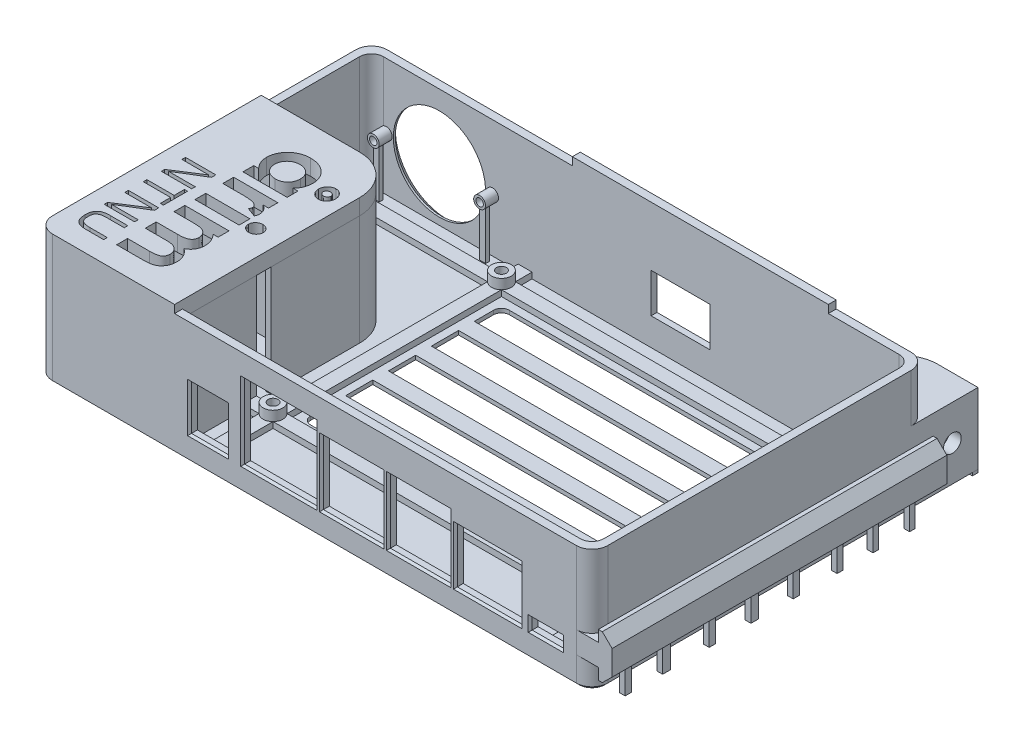
SolidWorks part; units mm, degrees
ref_plane "Plan de face" through (0, 0, 0) normal (0, 0, 1) x (1, 0, 0)
ref_plane "Plan de dessus" through (0, 0, 0) normal (0, 1, 0) x (1, 0, 0)
ref_plane "Plan de droite" through (0, 0, 0) normal (1, 0, 0) x (0, 0, -1)
sketch "Esquisse1" plane through (0, 0, 0) normal (0, 1, 0) x (1, 0, 0)
  line L2 (-70.5, -42.5) -> (70.5, -42.5)
  line L3 (-70.5, -42.5) -> (-70.5, 42.5)
  line L4 (-70.5, 42.5) -> (70.5, 42.5)
  line L5 (70.5, -42.5) -> (70.5, 42.5)
  line L6 (-70.5, -42.5) -> (70.5, 42.5) construction
  line L7 (-70.5, 42.5) -> (70.5, -42.5) construction
  point P2 (0, 0)
  dimension "D1" = 141
  dimension "D2" = 85
extrude "Main body" add sketch "Esquisse1" along normal blind 31
sketch "Esquisse2" plane through (0, 31, 0) normal (0, 1, 0) x (1, 0, 0)
  line L0 (70.5, -42.5) -> (70.5, 42.5) construction
  line L1 (-68.5, -40.5) -> (68.5, -40.5)
  line L2 (-68.5, -40.5) -> (-68.5, 40.5)
  line L3 (-68.5, 40.5) -> (68.5, 40.5)
  line L4 (68.5, -40.5) -> (68.5, 40.5)
  line L5 (-68.5, -40.5) -> (68.5, 40.5) construction
  line L6 (-68.5, 40.5) -> (68.5, -40.5) construction
  line L7 (70.5, 42.5) -> (-70.5, 42.5) construction
  point P0 (0, 0)
  dimension "D1" = 2
  dimension "D2" = 2
extrude "Body slot" cut sketch "Esquisse2" against normal blind 30
sketch "Esquisse3" plane through (0, 0, 42.5) normal (0, 0, 1) x (1, 0, 0)
  line L0 (68.5, 1) -> (68.5, 31) construction
  line L1 (55, 6.5) -> (62.5, 6.5) construction
  line L2 (55, 6.5) -> (55, 9) construction
  line L3 (55, 9) -> (62.5, 9) construction
  line L4 (62.5, 6.5) -> (62.5, 9) construction
  line L5 (55, 6.5) -> (62.5, 9) construction
  line L6 (55, 9) -> (62.5, 6.5) construction
  line L7 (68.5, 1) -> (-68.5, 1) construction
  line L9 (62.7, 6.3) -> (54.8, 6.3)
  line L10 (62.7, 6.3) -> (62.7, 9.2)
  line L11 (62.7, 9.2) -> (54.8, 9.2)
  line L12 (54.8, 6.3) -> (54.8, 9.2)
  line L13 (62.7, 6.3) -> (54.8, 9.2) construction
  line L14 (62.7, 9.2) -> (54.8, 6.3) construction
  line L15 (52, 6.5) -> (36, 6.5) construction
  line L16 (52, 6.5) -> (52, 20) construction
  line L17 (52, 20) -> (36, 20) construction
  line L18 (36, 6.5) -> (36, 20) construction
  line L19 (52, 6.5) -> (36, 20) construction
  line L20 (52, 20) -> (36, 6.5) construction
  line L21 (34, 6.5) -> (19, 6.5) construction
  line L22 (34, 6.5) -> (34, 22.5) construction
  line L23 (34, 22.5) -> (19, 22.5) construction
  line L24 (19, 6.5) -> (19, 22.5) construction
  line L25 (34, 6.5) -> (19, 22.5) construction
  line L26 (34, 22.5) -> (19, 6.5) construction
  line L27 (17, 6.5) -> (2, 6.5) construction
  line L28 (17, 6.5) -> (17, 22.5) construction
  line L29 (17, 22.5) -> (2, 22.5) construction
  line L30 (2, 6.5) -> (2, 22.5) construction
  line L31 (17, 6.5) -> (2, 22.5) construction
  line L32 (17, 22.5) -> (2, 6.5) construction
  line L33 (0, 6.5) -> (-18, 6.5) construction
  line L34 (0, 6.5) -> (0, 25) construction
  line L35 (0, 25) -> (-18, 25) construction
  line L36 (-18, 6.5) -> (-18, 25) construction
  line L37 (0, 6.5) -> (-18, 25) construction
  line L38 (0, 25) -> (-18, 6.5) construction
  line L39 (-22.5, 6.5) -> (-31.5, 6.5) construction
  line L40 (-22.5, 6.5) -> (-22.5, 17.5) construction
  line L41 (-22.5, 17.5) -> (-31.5, 17.5) construction
  line L42 (-31.5, 6.5) -> (-31.5, 17.5) construction
  line L43 (-22.5, 6.5) -> (-31.5, 17.5) construction
  line L44 (-22.5, 17.5) -> (-31.5, 6.5) construction
  line L45 (35.8, 6.3) -> (52.2, 6.3)
  line L46 (35.8, 6.3) -> (35.8, 20.2)
  line L47 (35.8, 20.2) -> (52.2, 20.2)
  line L48 (52.2, 6.3) -> (52.2, 20.2)
  line L49 (35.8, 6.3) -> (52.2, 20.2) construction
  line L50 (35.8, 20.2) -> (52.2, 6.3) construction
  line L51 (34.2, 6.3) -> (18.8, 6.3)
  line L52 (34.2, 6.3) -> (34.2, 22.7)
  line L53 (34.2, 22.7) -> (18.8, 22.7)
  line L54 (18.8, 6.3) -> (18.8, 22.7)
  line L55 (34.2, 6.3) -> (18.8, 22.7) construction
  line L56 (34.2, 22.7) -> (18.8, 6.3) construction
  line L57 (17.2, 6.3) -> (1.8, 6.3)
  line L58 (17.2, 6.3) -> (17.2, 22.7)
  line L59 (17.2, 22.7) -> (1.8, 22.7)
  line L60 (1.8, 6.3) -> (1.8, 22.7)
  line L61 (17.2, 6.3) -> (1.8, 22.7) construction
  line L62 (17.2, 22.7) -> (1.8, 6.3) construction
  line L63 (0.2, 6.3) -> (-18.2, 6.3)
  line L64 (0.2, 6.3) -> (0.2, 25.2)
  line L65 (0.2, 25.2) -> (-18.2, 25.2)
  line L66 (-18.2, 6.3) -> (-18.2, 25.2)
  line L67 (0.2, 6.3) -> (-18.2, 25.2) construction
  line L68 (0.2, 25.2) -> (-18.2, 6.3) construction
  line L69 (-22.3, 6.3) -> (-31.7, 6.3)
  line L70 (-22.3, 6.3) -> (-22.3, 17.7)
  line L71 (-22.3, 17.7) -> (-31.7, 17.7)
  line L72 (-31.7, 6.3) -> (-31.7, 17.7)
  line L73 (-22.3, 6.3) -> (-31.7, 17.7) construction
  line L74 (-22.3, 17.7) -> (-31.7, 6.3) construction
  point P0 (58.75, 7.75)
  point P5 (44, 13.25)
  point P10 (58.75, 7.75)
  point P19 (26.5, 14.5)
  point P24 (9.5, 14.5)
  point P29 (-9, 15.75)
  point P34 (-27, 12)
  point P39 (44, 13.25)
  point P44 (26.5, 14.5)
  point P49 (9.5, 14.5)
  point P54 (-9, 15.75)
  point P59 (-27, 12)
  dimension "D1" = 2.5
  dimension "D2" = 7.5
  dimension "D3" = 6
  dimension "D4" = 5.5
  dimension "D5" = 0.2
  dimension "D6" = 0.2
  dimension "D7" = 16
  dimension "D8" = 13.5
  dimension "D9" = 5.5
  dimension "D10" = 26.5
  dimension "D11" = 15
  dimension "D12" = 16
  dimension "D13" = 5.5
  dimension "D14" = 33
  dimension "D15" = 5.5
  dimension "D16" = 32
  dimension "D17" = 18
  dimension "D18" = 18.5
  dimension "D19" = 5.5
  dimension "D20" = 35
  dimension "D21" = 9
  dimension "D22" = 11
  dimension "D23" = 5.5
  dimension "D24" = 48.5
  dimension "D25" = 0.2
  dimension "D26" = 0.2
  dimension "D27" = 0.2
  dimension "D28" = 0.2
  dimension "D29" = 0.2
  dimension "D30" = 0.2
  dimension "D31" = 0.2
  dimension "D32" = 0.2
  dimension "D33" = 0.2
  dimension "D34" = 0.2
extrude "Jetson ports slot" cut sketch "Esquisse3" against normal blind 2
sketch "Esquisse4" plane through (0, 0, -42.5) normal (0, 0, -1) x (-1, 0, 0)
  line L0 (-68.5, 1) -> (-68.5, 31) construction
  line L1 (-4.5, 12) -> (-15.5, 12) construction
  line L2 (-4.5, 12) -> (-4.5, 14) construction
  line L3 (-4.5, 14) -> (-15.5, 14) construction
  line L4 (-15.5, 12) -> (-15.5, 14) construction
  line L5 (-4.5, 12) -> (-15.5, 14) construction
  line L6 (-4.5, 14) -> (-15.5, 12) construction
  line L7 (-68.5, 1) -> (68.5, 1) construction
  line L8 (68.5, 1) -> (68.5, 31) construction
  line L9 (-2.5, 8) -> (-17.5, 8)
  line L10 (-2.5, 8) -> (-2.5, 18)
  line L11 (-2.5, 18) -> (-17.5, 18)
  line L12 (-17.5, 8) -> (-17.5, 18)
  line L13 (-2.5, 8) -> (-17.5, 18) construction
  line L14 (-2.5, 18) -> (-17.5, 8) construction
  line L15 (67.5, 2.5) -> (35, 2.5) construction
  line L16 (67.5, 2.5) -> (67.5, 26.5) construction
  line L17 (67.5, 26.5) -> (35, 26.5) construction
  line L18 (35, 2.5) -> (35, 26.5) construction
  line L19 (67.5, 2.5) -> (35, 26.5) construction
  line L20 (67.5, 26.5) -> (35, 2.5) construction
  circle A0 centre (51.25, 14.5) radius 11.7
  point P0 (-10, 13)
  point P9 (-10, 13)
  point P14 (51.25, 14.5)
  dimension "D11" = 23.4
  dimension "D1" = 64
  dimension "D2" = 13
  dimension "D3" = 11
  dimension "D4" = 2
  dimension "D5" = 4
  dimension "D6" = 2
  dimension "D7" = 1
  dimension "D8" = 1.5
  dimension "D9" = 24
  dimension "D10" = 32.5
extrude "Sensor & SD slot" cut sketch "Esquisse4" against normal blind 2
fillet "Body corners" radius 4 4 edges at (70.5, 15.5, 42.5) (-70.5, 15.5, 42.5) (-70.5, 15.5, -42.5) (70.5, 15.5, -42.5)
fillet "Body interior corners" radius 3 4 edges at (68.5, 16, 40.5) (-68.5, 16, 40.5) (-68.5, 16, -40.5) (68.5, 16, -40.5)
chamfer "Body chanf" distance 0.75 angle 45 8 edges at (0, 0, 42.5) (69.3284, 0, 41.3284) (-69.3284, 0, 41.3284) (70.5, 0, 0) (-70.5, 0, 0) (69.3284, 0, -41.3284) (-69.3284, 0, -41.3284) (0, 0, -42.5)
chamfer "Ports chanf" distance 0.5 angle 45 28 edges at (17.5, 13, -42.5) (54.8, 7.75, 42.5) (58.75, 9.2, 42.5) (62.7, 7.75, 42.5) (58.75, 6.3, 42.5) (44, 20.2, 42.5) (52.2, 13.25, 42.5) (44, 6.3, 42.5) (35.8, 13.25, 42.5) (34.2, 14.5, 42.5) (26.5, 22.7, 42.5) (26.5, 6.3, 42.5) (18.8, 14.5, 42.5) (17.2, 14.5, 42.5) (9.5, 22.7, 42.5) (9.5, 6.3, 42.5) (1.8, 14.5, 42.5) (0.2, 15.75, 42.5) (-9, 25.2, 42.5) (-9, 6.3, 42.5) (-18.2, 15.75, 42.5) (-27, 17.7, 42.5) (-22.3, 12, 42.5) (-27, 6.3, 42.5) (-31.7, 12, 42.5) (2.5, 13, -42.5) (10, 8, -42.5) (10, 18, -42.5)
chamfer "Motion sensor chanf" distance 1.5 angle 45 1 edges at (-62.95, 14.5, -42.5)
sketch "Esquisse5" plane through (0, 1, 0) normal (0, 1, 0) x (1, 0, 0)
  line L0 (-65.5, -40.5) -> (65.5, -40.5) construction
  line L1 (56.5, -23.5) -> (-29.5, -23.5) construction
  line L2 (56.5, -23.5) -> (56.5, 34.5) construction
  line L3 (56.5, 34.5) -> (-29.5, 34.5) construction
  line L4 (-29.5, -23.5) -> (-29.5, 34.5) construction
  line L5 (56.5, -23.5) -> (-29.5, 34.5) construction
  line L6 (56.5, 34.5) -> (-29.5, -23.5) construction
  line L7 (68.5, -37.5) -> (68.5, 37.5) construction
  circle A0 centre (-29.5, 34.5) radius 2.5
  circle A1 centre (56.5, 34.5) radius 2.5
  circle A2 centre (56.5, -23.5) radius 2.5
  circle A3 centre (-29.5, -23.5) radius 2.5
  point P0 (13.5, 5.5)
  dimension "D5" = 5
  dimension "D1" = 17
  dimension "D2" = 12
  dimension "D3" = 86
  dimension "D4" = 58
extrude "Screws" add sketch "Esquisse5" along normal blind 4
sketch "Esquisse6" plane through (0, 1, 0) normal (0, 1, 0) x (1, 0, 0)
  line L0 (-68.5, 36.2678) -> (-31.2678, 36.2678)
  line L1 (-68.5, 37.5) -> (-68.5, -37.5) construction
  line L2 (-31.2678, 36.2678) -> (-31.2678, 40.5)
  line L3 (65.5, 40.5) -> (-65.5, 40.5) construction
  line L4 (-31.2678, 40.5) -> (-27.7322, 40.5)
  line L5 (-27.7322, 40.5) -> (-27.7322, 36.2678)
  line L6 (-27.7322, 36.2678) -> (54.7322, 36.2678)
  line L7 (54.7322, 36.2678) -> (54.7322, 40.5)
  line L8 (54.7322, 40.5) -> (58.2678, 40.5)
  line L9 (58.2678, 40.5) -> (58.2678, 36.2678)
  line L10 (58.2678, 36.2678) -> (68.5, 36.2678)
  line L11 (68.5, -37.5) -> (68.5, 37.5) construction
  line L12 (68.5, 36.2678) -> (68.5, 32.7322)
  line L13 (68.5, 32.7322) -> (58.2678, 32.7322)
  line L14 (58.2678, 32.7322) -> (58.2678, -21.7322)
  line L15 (58.2678, -21.7322) -> (68.5, -21.7322)
  line L16 (68.5, -37.5) -> (68.5, 37.5) construction
  line L17 (68.5, -21.7322) -> (68.5, -25.2678)
  line L18 (68.5, -25.2678) -> (58.2678, -25.2678)
  line L19 (58.2678, -25.2678) -> (58.2678, -40.5)
  line L20 (-65.5, -40.5) -> (65.5, -40.5) construction
  line L21 (58.2678, -40.5) -> (54.7322, -40.5)
  line L22 (54.7322, -40.5) -> (54.7322, -25.2678)
  line L23 (54.7322, -25.2678) -> (-27.7322, -25.2678)
  line L24 (-27.7322, -25.2678) -> (-27.7322, -40.5)
  line L25 (-27.7322, -40.5) -> (-31.2678, -40.5)
  line L26 (-31.2678, -40.5) -> (-31.2678, -25.2678)
  line L27 (-31.2678, -25.2678) -> (-68.5, -25.2678)
  line L28 (-68.5, -25.2678) -> (-68.5, -21.7322)
  line L29 (-68.5, -21.7322) -> (-31.2678, -21.7322)
  line L30 (-31.2678, -21.7322) -> (-31.2678, 32.7322)
  line L31 (-31.2678, 32.7322) -> (-68.5, 32.7322)
  line L33 (-68.5, 32.7322) -> (-68.5, 36.2678)
  line L34 (-27.7322, 32.7322) -> (-27.7322, -21.7322)
  line L35 (-27.7322, -21.7322) -> (54.7322, -21.7322)
  line L36 (54.7322, -21.7322) -> (54.7322, 32.7322)
  line L37 (54.7322, 32.7322) -> (-27.7322, 32.7322)
  line L38 (-68.5, 37.5) -> (-68.5, -37.5) construction
  line L39 (-27.7322, 32.7322) -> (-31.2678, 32.7322) construction
  line L40 (-27.7322, 32.7322) -> (-27.7322, 36.2678) construction
  line L41 (-27.7322, 36.2678) -> (-31.2678, 36.2678) construction
  line L42 (-31.2678, 32.7322) -> (-31.2678, 36.2678) construction
  line L43 (-27.7322, 32.7322) -> (-31.2678, 36.2678) construction
  line L44 (-27.7322, 36.2678) -> (-31.2678, 32.7322) construction
  line L45 (58.2678, 32.7322) -> (54.7322, 32.7322) construction
  line L46 (58.2678, 32.7322) -> (58.2678, 36.2678) construction
  line L47 (58.2678, 36.2678) -> (54.7322, 36.2678) construction
  line L48 (54.7322, 32.7322) -> (54.7322, 36.2678) construction
  line L49 (58.2678, 32.7322) -> (54.7322, 36.2678) construction
  line L50 (58.2678, 36.2678) -> (54.7322, 32.7322) construction
  line L51 (-27.7322, -25.2678) -> (-31.2678, -25.2678) construction
  line L52 (-27.7322, -25.2678) -> (-27.7322, -21.7322) construction
  line L53 (-27.7322, -21.7322) -> (-31.2678, -21.7322) construction
  line L54 (-31.2678, -25.2678) -> (-31.2678, -21.7322) construction
  line L55 (-27.7322, -25.2678) -> (-31.2678, -21.7322) construction
  line L56 (-27.7322, -21.7322) -> (-31.2678, -25.2678) construction
  line L57 (54.7322, -25.2678) -> (58.2678, -25.2678) construction
  line L58 (54.7322, -25.2678) -> (54.7322, -21.7322) construction
  line L59 (54.7322, -21.7322) -> (58.2678, -21.7322) construction
  line L60 (58.2678, -25.2678) -> (58.2678, -21.7322) construction
  line L61 (54.7322, -25.2678) -> (58.2678, -21.7322) construction
  line L62 (54.7322, -21.7322) -> (58.2678, -25.2678) construction
  circle A0 centre (-29.5, -23.5) radius 2.5 construction
  circle A1 centre (-29.5, 34.5) radius 2.5 construction
  circle A2 centre (56.5, 34.5) radius 2.5 construction
  circle A3 centre (-29.5, -23.5) radius 2.5 construction
  circle A4 centre (56.5, -23.5) radius 2.5 construction
  point P10 (-29.5, -23.5)
  point P40 (56.5, -23.5)
  point P46 (-29.5, 34.5)
  point P71 (56.5, 34.5)
extrude "Reinforcement" add sketch "Esquisse6" along normal blind 1.5
sketch "Esquisse7" plane through (0, 1, 0) normal (0, 1, 0) x (1, 0, 0)
  line L0 (-25.7322, 107.0302) -> (-25.7322, 77.7826) construction
  line L1 (52.7322, 23.8393) -> (-25.7322, 23.8393)
  line L2 (52.7322, 23.8393) -> (52.7322, 30.7322)
  line L3 (52.7322, 30.7322) -> (-25.7322, 30.7322)
  line L4 (-25.7322, 23.8393) -> (-25.7322, 30.7322)
  line L5 (52.7322, 23.8393) -> (-25.7322, 30.7322) construction
  line L6 (52.7322, 30.7322) -> (-25.7322, 23.8393) construction
  line L7 (52.7322, 8.9464) -> (-25.7322, 8.9464)
  line L8 (52.7322, 8.9464) -> (52.7322, 2.0536)
  line L9 (52.7322, 2.0536) -> (-25.7322, 2.0536)
  line L10 (-25.7322, 8.9464) -> (-25.7322, 2.0536)
  line L11 (52.7322, 8.9464) -> (-25.7322, 2.0536) construction
  line L12 (52.7322, 2.0536) -> (-25.7322, 8.9464) construction
  line L13 (52.7322, 19.8393) -> (-25.7322, 19.8393)
  line L14 (52.7322, 19.8393) -> (52.7322, 12.9464)
  line L15 (52.7322, 12.9464) -> (-25.7322, 12.9464)
  line L16 (-25.7322, 19.8393) -> (-25.7322, 12.9464)
  line L17 (52.7322, 19.8393) -> (-25.7322, 12.9464) construction
  line L18 (52.7322, 12.9464) -> (-25.7322, 19.8393) construction
  line L19 (52.7322, -8.8393) -> (-25.7322, -8.8393)
  line L20 (52.7322, -8.8393) -> (52.7322, -1.9464)
  line L21 (52.7322, -1.9464) -> (-25.7322, -1.9464)
  line L22 (-25.7322, -8.8393) -> (-25.7322, -1.9464)
  line L23 (52.7322, -8.8393) -> (-25.7322, -1.9464) construction
  line L24 (52.7322, -1.9464) -> (-25.7322, -8.8393) construction
  line L25 (52.7322, -19.7322) -> (-25.7322, -19.7322)
  line L26 (52.7322, -19.7322) -> (52.7322, -12.8393)
  line L27 (52.7322, -12.8393) -> (-25.7322, -12.8393)
  line L28 (-25.7322, -19.7322) -> (-25.7322, -12.8393)
  line L29 (52.7322, -19.7322) -> (-25.7322, -12.8393) construction
  line L30 (52.7322, -12.8393) -> (-25.7322, -19.7322) construction
  line L31 (54.7322, 32.7322) -> (-27.7322, 32.7322) construction
  line L32 (-27.7322, 32.7322) -> (-27.7322, -21.7322) construction
  line L33 (54.7322, -21.7322) -> (54.7322, 32.7322) construction
  line L34 (-27.7322, -21.7322) -> (54.7322, -21.7322) construction
  point P0 (13.5, 27.2858)
  point P5 (13.5, 5.5)
  point P10 (13.5, 16.3929)
  point P15 (13.5, -5.3929)
  point P20 (13.5, -16.2858)
  dimension "D1" = 4
  dimension "D2" = 4
  dimension "D3" = 4
  dimension "D4" = 4
  dimension "D5" = 2
  dimension "D6" = 2
  dimension "D7" = 2
  dimension "D8" = 2
extrude "Heat" cut sketch "Esquisse7" against normal blind 2
fillet "Congé3" radius 2 4 edges at (52.7322, 0.5, 19.7322) (-25.7322, 0.5, 19.7322) (52.7322, 0.5, -30.7322) (-25.7322, 0.5, -30.7322)
sketch "Esquisse8" plane through (0, 5, 0) normal (0, 1, 0) x (1, 0, 0)
  circle A0 centre (-29.5, -23.5) radius 1.25
  circle A1 centre (-29.5, 34.5) radius 1.25
  circle A2 centre (56.5, 34.5) radius 1.25
  circle A3 centre (56.5, -23.5) radius 1.25
  dimension "D1" = 2.5
extrude "Screw holes" cut sketch "Esquisse8" against normal through all
sketch "Esquisse9" plane through (70.5, 0, 0) normal (1, 0, 0) x (0, 0, -1)
  line L0 (42.5, 31) -> (42.5, 0.75) construction
  line L1 (-42.5, 12.5) -> (42.5, 12.5)
  line L2 (-42.5, 12.5) -> (-42.5, 7)
  line L3 (-42.5, 7) -> (42.5, 7)
  line L4 (42.5, 12.5) -> (42.5, 7)
  line L5 (-42.5, 0.75) -> (-42.5, 31) construction
  line L6 (38.5, 0) -> (-38.5, 0) construction
  dimension "D1" = 7
  dimension "D2" = 5.5
extrude "Boss.-Extru.3" add sketch "Esquisse9" along normal blind 1.6 and the other way blind 1.6
sketch "Esquisse10" plane through (72.1, 0, 0) normal (1, 0, 0) x (0, 0, -1)
  line L0 (-42.5, 7) -> (42.5, 7) construction
  line L1 (-42.5, 12.5) -> (-40.5, 12.5)
  line L2 (-42.5, 12.5) -> (-42.5, 7)
  line L3 (-42.5, 7) -> (-40.5, 7)
  line L4 (-40.5, 12.5) -> (-40.5, 7)
  line L6 (42.5, 12.5) -> (40.5, 12.5)
  line L7 (42.5, 12.5) -> (42.5, 7)
  line L8 (42.5, 7) -> (40.5, 7)
  line L9 (40.5, 12.5) -> (40.5, 7)
  dimension "D1" = 2
  dimension "D2" = 2
extrude "Boss.-Extru.4" add sketch "Esquisse10" against normal blind 5.5
sketch "Esquisse12" plane through (72.1, 0, 0) normal (1, 0, 0) x (0, 0, -1)
  line L0 (42.5, 31) -> (42.5, 0.75) construction
  line L1 (42.5, 7) -> (-42.5, 7) construction
  line L2 (42.5, 7) -> (42.5, 12.5) construction
  line L3 (42.5, 12.5) -> (-42.5, 12.5) construction
  line L4 (-42.5, 7) -> (-42.5, 12.5) construction
  line L5 (42.5, 7) -> (-42.5, 12.5) construction
  line L6 (42.5, 12.5) -> (-42.5, 7) construction
  line L7 (-42.5, 4.15) -> (42.5, 4.15)
  line L8 (-42.5, 4.15) -> (-42.5, 15.35)
  line L9 (-42.5, 15.35) -> (42.5, 15.35)
  line L10 (42.5, 4.15) -> (42.5, 15.35)
  line L11 (-42.5, 4.15) -> (42.5, 15.35) construction
  line L12 (-42.5, 15.35) -> (42.5, 4.15) construction
  point P0 (0, 9.75)
  point P8 (0, 9.75)
  dimension "D1" = 11.2
extrude "Boss.-Extru.5" add sketch "Esquisse12" along normal blind 3.5
sketch "Esquisse13" plane through (0, 0, -42.5) normal (0, 0, -1) x (-1, 0, 0)
  line L0 (-72.1, 12.5) -> (-72.1, 15.35) construction
  line L1 (-72.1, 15.35) -> (-73.1, 15.35) construction
  line L2 (-75.6, 15.35) -> (-72.1, 15.35) construction
  line L3 (-73.1, 15.35) -> (-75.6, 12.9) construction
  line L4 (-75.6, 4.15) -> (-75.6, 15.35) construction
  line L5 (-75.6, 12.9) -> (-75.6, 6.6) construction
  line L6 (-75.6, 6.6) -> (-73.1, 4.15) construction
  line L7 (-75.6, 4.15) -> (-72.1, 4.15) construction
  line L8 (-73.1, 4.15) -> (-72.1, 4.15) construction
  line L9 (-72.1, 4.15) -> (-72.1, 12.5) construction
  line L10 (-72.1, 12.5) -> (-72.1, 15.35) construction
  line L11 (-73.1, 15.35) -> (-75.6, 15.35)
  line L12 (-75.6, 15.35) -> (-75.6, 12.9)
  line L13 (-75.6, 12.9) -> (-73.1, 15.35)
  line L14 (-75.6, 6.6) -> (-75.6, 4.15)
  line L15 (-75.6, 4.15) -> (-73.1, 4.15)
  line L16 (-73.1, 4.15) -> (-75.6, 6.6)
  dimension "D1" = 1
  dimension "D2" = 1
  dimension "D3" = 6.3
extrude "Enlèv. mat.-Extru.6" cut sketch "Esquisse13" against normal through all
sketch "Esquisse14" plane through (0, 0, -42.5) normal (0, 0, -1) x (-1, 0, 0)
  line L0 (-66.6, 12.5) -> (-72.1, 12.5) construction
  line L1 (-70.5, 0.75) -> (-50.3729, 0.75)
  line L2 (-70.5, 0.75) -> (-70.5, 18.75)
  line L3 (-70.5, 18.75) -> (-50.3729, 18.75)
  line L4 (-50.3729, 0.75) -> (-50.3729, 18.75)
  line L5 (-70.5, 7) -> (-66.6, 7) construction
  line L6 (-70.5, 7) -> (-70.5, 12.5) construction
  line L7 (-70.5, 12.5) -> (-66.6, 12.5) construction
  line L8 (-66.6, 7) -> (-66.6, 12.5) construction
  line L9 (-70.5, 7) -> (-66.6, 12.5) construction
  line L10 (-70.5, 12.5) -> (-66.6, 7) construction
  line L11 (-66.6, 7) -> (-66.6, 12.5) construction
  line L12 (-66.6, 7) -> (-72.1, 7) construction
  point P5 (-68.55, 9.75)
  dimension "D1" = 18
  dimension "D2" = 20.1271
extrude "Boss.-Extru.6" add sketch "Esquisse14" along normal blind 13 and the other way blind 2
sketch "Esquisse15" plane through (0, 0, -55.5) normal (0, 0, -1) x (-1, 0, 0)
  line L0 (-66.5, 0.75) -> (-50.3729, 0.75) construction
  line L1 (-70.5, 18.75) -> (-68.5, 18.75)
  line L2 (-70.5, 18.75) -> (-70.5, 0.75)
  line L3 (-70.5, 0.75) -> (-68.5, 0.75)
  line L4 (-68.5, 18.75) -> (-68.5, 0.75)
  dimension "D1" = 2
extrude "Boss.-Extru.7" add sketch "Esquisse15" against normal blind 25
sketch "Esquisse16" plane through (0, 0, -55.5) normal (0, 0, -1) x (-1, 0, 0)
  line L0 (-50.3729, 18.75) -> (-50.3729, 0.75) construction
  line L1 (-50.3729, 3.25) -> (-67.5, 3.25)
  line L2 (-50.3729, 3.25) -> (-50.3729, 16.25)
  line L3 (-50.3729, 16.25) -> (-67.5, 16.25)
  line L4 (-67.5, 3.25) -> (-67.5, 16.25)
  line L5 (-66.5, 18.75) -> (-50.3729, 18.75) construction
  line L6 (-66.5, 0.75) -> (-50.3729, 0.75) construction
  line L7 (-70.5, 18.75) -> (-70.5, 0.75) construction
  dimension "D1" = 2.5
  dimension "D2" = 2.5
  dimension "D3" = 3
extrude "Enlèv. mat.-Extru.7" cut sketch "Esquisse16" against normal blind 13
fillet "Congé6" radius 10 2 edges at (50.3729, 2, -55.5) (50.3729, 17.5, -55.5)
sketch "Esquisse17" plane through (67.5, 0, 0) normal (-1, 0, 0) x (0, 0, 1)
  line L1 (-42.5, 3.25) -> (-55.5, 3.25) construction
  line L2 (-42.5, 3.25) -> (-42.5, 16.25) construction
  line L3 (-42.5, 16.25) -> (-55.5, 16.25) construction
  line L4 (-55.5, 3.25) -> (-55.5, 16.25) construction
  line L5 (-42.5, 3.25) -> (-55.5, 16.25) construction
  line L6 (-42.5, 16.25) -> (-55.5, 3.25) construction
  circle A0 centre (-49, 9.75) radius 2.25
  point P0 (-49, 9.75)
  dimension "D1" = 4.5
extrude "Enlèv. mat.-Extru.8" cut sketch "Esquisse17" against normal through all
sketch "Esquisse18" plane through (0, 0, -40.5) normal (0, 0, 1) x (1, 0, 0)
  line L0 (-50.9443, 14.5) -> (-44.062, 14.5) construction
  circle A0 centre (-64.75, 14.5) radius 1.5
  circle A1 centre (-37.75, 14.5) radius 1.5
  dimension "D3" = 3
  dimension "D4" = 3
  dimension "D1" = 13.5
  dimension "D2" = 13.5
extrude "Boss.-Extru.8" add sketch "Esquisse18" along normal blind 3.3
sketch "Esquisse19" plane through (0, 0, -37.2) normal (0, 0, 1) x (1, 0, 0)
  circle A0 centre (-64.75, 14.5) radius 0.95
  circle A1 centre (-37.75, 14.5) radius 0.95
  dimension "D1" = 1.9
  dimension "D2" = 1.9
extrude "Enlèv. mat.-Extru.9" cut sketch "Esquisse19" against normal blind 3.3
sketch "Esquisse21" plane through (0, 31, 0) normal (0, 1, 0) x (1, 0, 0)
  line L0 (-70.5, -38.5) -> (-70.5, 14.5)
  line L1 (-70.5, 38.5) -> (-70.5, -38.5) construction
  line L2 (-70.5, 14.5) -> (-35.5, 14.5)
  line L3 (-35.5, 14.5) -> (-35.5, -42.5)
  line L4 (-66.5, -42.5) -> (66.5, -42.5) construction
  line L5 (-35.5, -42.5) -> (-66.5, -42.5)
  line L12 (66.5, 42.5) -> (-66.5, 42.5) construction
  line L13 (-17.5, 42.5) -> (47.5, 42.5)
  line L14 (-17.5, 42.5) -> (-17.5, 40.5)
  line L15 (-17.5, 40.5) -> (47.5, 40.5)
  line L16 (47.5, 42.5) -> (47.5, 40.5)
  line L17 (65.5, 40.5) -> (-65.5, 40.5) construction
  line L18 (68.5, -37.5) -> (68.5, 37.5) construction
  arc A0 (-70.5, -38.5) -> (-66.5, -42.5) centre (-66.5, -38.5) ccw construction
  arc A1 (-70.5, -38.5) -> (-66.5, -42.5) centre (-66.5, -38.5) ccw
  dimension "D1" = 35
  dimension "D2" = 57
  dimension "D5" = 21
  dimension "D6" = 65
extrude "Boss.-Extru.9" add sketch "Esquisse21" along normal blind 2 and the other way blind 2
fillet "Congé7" radius 10 1 edges at (-35.5, 31, -14.5)
sketch "Esquisse27" plane through (0, 33, 0) normal (0, 1, 0) x (1, 0, 0)
  line L0 (-55.9779, 13.1597) -> (-55.9779, -37.9046) construction
  line L1 (-66.4626, 8.5102) -> (-66.4626, -37.9046) construction
  text T0 "<b>årim</b>" font "Century Gothic" height in points 58
  text T1 "<b>NTNU</b>" font "Microsoft Yi Baiti" height in points 25
extrude "Logo" cut sketch "Esquisse27" against normal blind 4
sketch "Esquisse28" plane through (0, 29, 0) normal (0, -1, 0) x (1, 0, 0)
  line L0 (-45.5, -14.5) -> (-68.5, -14.5) construction
  line L1 (-45.5, -14.5) -> (-68.5, -14.5)
  line L12 (-35.5, 40.5) -> (-35.5, -4.5) construction
  line L13 (-31.2678, 21.7322) -> (-68.5, 21.7322) construction
  line L14 (-35.5, -4.5) -> (-35.5, 18)
  line L15 (-35.5, 18) -> (-36.9015, 18)
  line L17 (-36.9015, -4.5) -> (-45.5, -13.0985)
  line L19 (-68.5, -32.7322) -> (-68.5, 21.7322) construction
  line L20 (-68.5, -13.0985) -> (-68.5, -14.5)
  line L22 (66.5, 41.75) -> (-66.5, 41.75) construction
  line L24 (-68.5, 25.2678) -> (-31.2678, 25.2678) construction
  line L26 (-41.2007, 25.2678) -> (-41.2007, 38.1838)
  line L27 (-41.2007, 38.1838) -> (-36.9015, 38.1838)
  line L28 (-36.9015, 38.1838) -> (-36.9015, 25.2678)
  line L29 (-36.9015, 25.2678) -> (-36.9015, 21.7322)
  line L30 (-36.9015, 21.7322) -> (-35.5, 21.7322)
  line L31 (-68.5, -13.0985) -> (-64.7371, -13.0985)
  line L32 (-64.7371, -13.0985) -> (-64.7371, 6.75)
  line L33 (-64.7371, 6.75) -> (-58.7074, 6.75)
  line L34 (-58.7074, 6.75) -> (-58.7074, 5.3094)
  line L35 (-58.7074, 5.3094) -> (-63.3934, 5.3094)
  line L36 (-63.3934, 5.3094) -> (-63.3934, 0.507)
  line L37 (-63.3934, 0.507) -> (-58.7074, 0.507)
  line L38 (-58.7074, 0.507) -> (-58.7074, -0.7817)
  line L39 (-58.7074, -0.7817) -> (-63.3934, -0.7817)
  line L40 (-63.3934, -0.7817) -> (-63.3934, -6.487)
  line L41 (-63.3934, -6.487) -> (-58.7074, -6.487)
  line L42 (-58.7074, -6.487) -> (-58.7074, -8.1655)
  line L43 (-58.7074, -8.1655) -> (-63.3934, -8.1655)
  line L44 (-63.3934, -8.1655) -> (-63.3934, -13.0985)
  line L45 (-63.3934, -13.0985) -> (-55.966, -13.0985)
  line L46 (-55.966, -13.0985) -> (-55.966, -8.1655)
  line L47 (-55.966, -8.1655) -> (-54.1792, -8.1655)
  line L48 (-54.1792, -8.1655) -> (-54.1792, -13.0985)
  line L49 (-54.1792, -13.0985) -> (-51.0119, -13.0985)
  line L50 (-51.0119, -13.0985) -> (-51.0119, -10.632)
  line L51 (-51.0119, -10.632) -> (-50.0373, -10.632)
  line L52 (-50.0373, -10.632) -> (-50.0373, -13.0985)
  line L53 (-50.0373, -13.0985) -> (-46.9918, -13.0985)
  line L54 (-46.9918, -13.0985) -> (-46.9918, -8.7993)
  line L55 (-46.9918, -8.7993) -> (-45.5, -8.7993)
  line L56 (-45.5, -8.7993) -> (-45.5, -13.0985)
  line L57 (-36.9015, 18) -> (-36.9015, 9.8568)
  line L58 (-36.9015, 9.8568) -> (-42.6309, 9.8568)
  line L59 (-42.6309, 9.8568) -> (-42.6309, 8.7695)
  line L60 (-42.6309, 8.7695) -> (-36.9015, 8.7695)
  line L61 (-36.9015, 8.7695) -> (-36.9015, 4.7734)
  line L62 (-36.9015, 4.7734) -> (-42.6309, 4.7734)
  line L63 (-42.6309, 4.7734) -> (-42.6309, 3.3046)
  line L64 (-42.6309, 3.3046) -> (-36.9015, 3.3046)
  line L65 (-36.9015, 3.3046) -> (-36.9015, -4.5)
  line L68 (-50.34, 39.1839) -> (-52.7625, 39.1839)
  line L69 (-52.7625, 39.1839) -> (-52.7625, 37.5632)
  line L70 (-52.7625, 37.5632) -> (-53.7613, 37.5632)
  line L71 (-53.7613, 37.5632) -> (-53.7613, 39.1839)
  line L73 (-56.7569, 38.6521) -> (-56.7569, 32.1424)
  line L74 (-56.7569, 32.1424) -> (-49.6152, 32.1424)
  line L75 (-49.6152, 32.1424) -> (-49.6152, 31.3855)
  line L76 (-49.6152, 31.3855) -> (-56.733, 31.3855)
  line L77 (-56.733, 31.3855) -> (-56.733, 25.2678)
  line L78 (-56.733, 25.2678) -> (-49.6152, 25.2678)
  line L79 (-49.6152, 25.2678) -> (-49.6152, 24.1052)
  line L80 (-49.6152, 24.1052) -> (-56.6611, 24.1052)
  line L81 (-56.6611, 24.1052) -> (-56.6611, 18.6215)
  line L82 (-56.6611, 18.6215) -> (-45.5, 18.6215)
  line L83 (-45.5, 18.6215) -> (-45.5, 18)
  line L84 (-45.5, 18) -> (-57.5884, 18)
  line L85 (-57.5884, 18) -> (-57.5884, 26.5264)
  line L86 (-57.5884, 26.5264) -> (-60.1062, 26.5264)
  line L87 (-60.1062, 26.5264) -> (-60.1062, 27.5039)
  line L88 (-60.1062, 27.5039) -> (-57.5884, 27.5039)
  line L89 (-57.5884, 27.5039) -> (-57.5884, 29.9518)
  line L93 (-57.5884, 30.6512) -> (-57.5884, 33.6282)
  line L94 (-57.5884, 33.6282) -> (-64.3026, 33.6282)
  line L95 (-64.3026, 33.6282) -> (-64.3026, 34.6378)
  line L96 (-64.3026, 34.6378) -> (-57.5884, 34.6378)
  line L99 (-61.4351, 21.7322) -> (-61.4351, 20.7197)
  line L100 (-61.4351, 20.7197) -> (-67.5713, 20.7197)
  line L101 (-67.5713, 20.7197) -> (-67.5713, 17.3626)
  line L102 (-67.5713, 17.3626) -> (-60.7357, 17.3626)
  line L103 (-60.7357, 17.3626) -> (-60.7357, 16.2436)
  line L104 (-60.7357, 16.2436) -> (-67.5199, 16.2436)
  line L105 (-67.5199, 16.2436) -> (-67.5199, 11.8746)
  line L106 (-67.5199, 11.8746) -> (-64.9675, 11.8746)
  line L107 (-64.9675, 11.8746) -> (-64.9675, 11.068)
  line L108 (-64.9675, 11.068) -> (-67.5199, 11.068)
  line L109 (-67.5199, 11.068) -> (-67.5199, 9.5293)
  line L112 (-68.5, 26.5264) -> (-64.9675, 26.5264)
  line L113 (-68.5, 25.2678) -> (-68.5, 37.5) construction
  line L114 (-64.9675, 26.5264) -> (-64.9675, 25.2678)
  line L115 (-64.9675, 25.2678) -> (-68.5, 25.2678)
  line L116 (-68.5, 25.2678) -> (-68.5, 26.5264)
  line L117 (-57.5884, 34.6378) -> (-57.5884, 38.1838)
  line L118 (-57.5884, 38.1838) -> (-65.7014, 38.1838)
  line L119 (-65.7014, 38.1838) -> (-65.7014, 38.6521)
  line L120 (-65.7014, 38.6521) -> (-57.5884, 38.6521)
  line L122 (-42.6309, 25.2678) -> (-42.6309, 21.7322)
  line L123 (-42.6309, 21.7322) -> (-41.2007, 21.7322)
  line L124 (-41.2007, 21.7322) -> (-41.2007, 25.2678)
  line L125 (-60.1062, 12.8864) -> (-48.5661, 12.8864)
  line L126 (-48.5661, 12.8864) -> (-48.5661, 11.5576)
  line L127 (-48.5661, 11.5576) -> (-60.1062, 11.5576)
  line L128 (-60.1062, 11.5576) -> (-60.1062, 12.8864)
  line L129 (-55.9098, 6.2421) -> (-55.9098, 5.6826)
  line L130 (-55.9098, 5.6826) -> (-44.8592, 5.6826)
  line L131 (-57.5884, 30.6512) -> (-57.5884, 29.9518)
  line L132 (-55.9098, 6.2421) -> (-44.8592, 6.2421)
  line L133 (-44.8592, 6.2421) -> (-44.8592, 5.6826)
  line L134 (-67.5713, 30.6876) -> (-67.5713, 29.8716)
  line L136 (-59.4408, 29.8716) -> (-59.4408, 30.6876)
  line L138 (-67.5713, 30.6876) -> (-66.1062, 30.6876)
  line L139 (-66.1062, 30.6876) -> (-66.1062, 29.8716)
  line L140 (-66.1062, 29.8716) -> (-67.5713, 29.8716)
  line L141 (-59.4408, 30.6876) -> (-61.1661, 30.6876)
  line L142 (-61.1661, 30.6876) -> (-61.1661, 29.8716)
  line L143 (-61.1661, 29.8716) -> (-59.4408, 29.8716)
  line L144 (-47.1245, 39.0239) -> (-47.1245, 38.1838)
  line L145 (-47.1245, 38.1838) -> (-45.5, 38.1838)
  line L146 (-45.5, 38.1838) -> (-45.5, 39.0239)
  line L147 (-45.5, 39.0239) -> (-47.1245, 39.0239)
  line L148 (-40.0725, 13.271) -> (-40.0725, 12.257)
  line L149 (-40.0725, 12.257) -> (-38.4173, 12.257)
  line L150 (-38.4173, 12.257) -> (-38.4173, 13.271)
  line L151 (-38.4173, 13.271) -> (-40.0725, 13.271)
  line L152 (-57.5884, 38.6521) -> (-57.5884, 39.7488)
  line L153 (-57.5884, 39.7488) -> (-48.9706, 39.7488)
  line L154 (-48.9706, 39.7488) -> (-48.9706, 37.7057)
  line L155 (-48.9706, 37.7057) -> (-49.4298, 37.7057)
  line L156 (-49.4298, 37.7057) -> (-49.4298, 39.1839)
  line L157 (-49.4298, 39.1839) -> (-50.34, 39.1839)
  line L158 (-53.7613, 39.1839) -> (-56.7569, 39.1839)
  line L159 (-56.7569, 39.1839) -> (-56.7569, 38.6521)
  line L160 (-61.4351, 21.7322) -> (-64.0366, 21.7322)
  line L161 (-64.0366, 21.7322) -> (-64.0366, 22.5233)
  line L162 (-64.0366, 22.5233) -> (-64.5652, 22.5233)
  line L163 (-64.5652, 22.5233) -> (-64.5652, 21.7322)
  line L164 (-64.5652, 21.7322) -> (-67.149, 21.7322)
  line L165 (-67.149, 21.7322) -> (-67.149, 23.737)
  line L166 (-67.149, 23.737) -> (-67.5713, 23.737)
  line L167 (-67.5713, 23.737) -> (-67.5713, 21.7322)
  line L168 (-67.5713, 21.7322) -> (-67.8733, 21.7322)
  line L169 (-67.8733, 21.7322) -> (-67.8733, 9.5293)
  line L170 (-67.8733, 9.5293) -> (-67.5199, 9.5293)
  line L171 (-67.5199, 2.8613) -> (-67.5199, 2.0977)
  line L172 (-67.5199, 2.0977) -> (-66.4857, 2.0977)
  line L173 (-66.4857, 2.0977) -> (-66.4857, 2.8613)
  line L174 (-66.4857, 2.8613) -> (-67.5199, 2.8613)
  line L175 (-67.5199, -3.9431) -> (-67.5199, -4.9309)
  line L176 (-67.5199, -4.9309) -> (-66.4857, -4.9309)
  line L177 (-66.4857, -4.9309) -> (-66.4857, -3.9431)
  line L178 (-66.4857, -3.9431) -> (-67.5199, -3.9431)
  line L179 (-42.6309, 25.2678) -> (-42.6309, 41.75)
  line L180 (-42.6309, 41.75) -> (-35.5, 41.75)
  line L181 (-35.5, 41.75) -> (-35.5, 21.7322)
  line L182 (-35.5, 40.5) -> (-35.5, 42.5) construction
  arc A0 (-45.5, -14.5) -> (-35.5, -4.5) centre (-45.5, -4.5) ccw construction
  arc A1 (-45.5, -14.5) -> (-35.5, -4.5) centre (-45.5, -4.5) ccw
  spline S0 degree 3 poles (4899.5335, -777.716) (-95.5929, 18.1276) (-37.8587, 3.5856) (-39.5171, -1.4906) (-39.6079, -1.6442) (-39.7353, -1.7771) (-39.8841, -1.8908) (-40.0517, -1.9746) (-45.6583, -3.5647) (-59.2873, 55.9451) (598.8171, -4960.6472) knots -10.469034 -10.469034 -10.469034 -10.469034 0.120361 0.237247 0.356818 0.483115 0.612056 0.738841 0.86519 12.447258 12.447258 12.447258 12.447258 only from (-39.4516, -1.1485) to (-40.4292, -2.0339) construction
  spline S1 degree 3 poles (-665.5839, -4962.5256) (-21.513, 55.2216) (-35.0409, -3.5533) (-40.8147, -1.9751) (-40.9869, -1.8918) (-41.1356, -1.7738) (-41.2608, -1.6387) (-41.3544, -1.4871) (-42.9918, 3.6171) (13.6131, 17.4311) (-4987.6456, -730.2306) knots -11.689455 -11.689455 -11.689455 -11.689455 0.135957 0.265459 0.393237 0.522554 0.649512 0.766467 0.882544 11.427763 11.427763 11.427763 11.427763 only from (-40.4292, -2.0339) to (-41.419, -1.1485) construction
  spline S2 degree 3 poles (644.2162, 4952.3832) (-59.7983, -58.7628) (-45.5908, 1.284) (-40.0525, -0.3232) (-39.8834, -0.4027) (-39.7343, -0.5171) (-39.6089, -0.6527) (-39.517, -0.8064) (-37.8609, -5.8953) (-95.5214, -20.2481) (4902.0536, 759.9869) knots -11.328725 -11.328725 -11.328725 -11.328725 0.134726 0.260998 0.38678 0.515641 0.643403 0.7629 0.879713 11.480516 11.480516 11.480516 11.480516 only from (-40.4292, -0.2632) to (-39.4516, -1.1485) construction
  spline S3 degree 3 poles (-4975.3417, 806.7119) (14.9054, -20.6048) (-43.0177, -5.7678) (-41.3529, -0.8118) (-41.262, -0.6586) (-41.1353, -0.5237) (-40.9878, -0.4043) (-40.8133, -0.3268) (-35.3753, 1.3517) (-20.1047, -60.4326) (-794.5708, 4942.2138) knots -10.179941 -10.179941 -10.179941 -10.179941 0.11752 0.231676 0.350485 0.477513 0.606901 0.733843 0.863968 12.109905 12.109905 12.109905 12.109905 only from (-41.419, -1.1485) to (-40.4292, -0.2632) construction
  spline S4 degree 3 poles (-301.7908, -4997.495) (-24.4891, 45.1951) (-39.1971, -5.5209) (-51.0283, -4.149) (-51.3479, -4.0784) (-51.6494, -3.975) (-51.9383, -3.85) (-52.2091, -3.6925) (-52.4628, -3.5051) (-52.7016, -3.2961) (-52.9133, -3.0626) (-53.106, -2.8193) (-53.2602, -2.5567) (-53.3919, -2.2839) (-53.4932, -1.9985) (-53.5642, -1.6985) (-55.0129, 8.7044) (-1.3563, 22.8665) (-5043.0671, -320.0407) knots -6.85008 -6.85008 -6.85008 -6.85008 0.068712 0.135395 0.199506 0.262323 0.324065 0.385851 0.447575 0.510836 0.573603 0.634235 0.694452 0.753686 0.813632 0.8736 0.936143 7.027352 7.027352 7.027352 7.027352 only from (-50.3492, -4.198) to (-53.617, -1.0655) construction
  spline S5 degree 3 poles (-5045.7936, 271.5541) (-3.6486, -26.096) (-54.9478, -11.6935) (-53.5676, -0.413) (-53.4974, -0.1067) (-53.3935, 0.1834) (-53.2684, 0.4614) (-53.1141, 0.7252) (-52.9267, 0.9711) (-52.7178, 1.2049) (-52.4798, 1.4114) (-52.2285, 1.5989) (-51.955, 1.7526) (-51.6654, 1.8787) (-51.3585, 1.9776) (-51.0345, 2.0488) (-38.9148, 3.4196) (-24.1475, -47.4313) (-278.5425, 4996.3231) knots -6.468475 -6.468475 -6.468475 -6.468475 0.065619 0.128649 0.189771 0.249683 0.309159 0.368464 0.428601 0.490333 0.552111 0.613215 0.674082 0.735755 0.798324 0.862966 0.930175 7.944065 7.944065 7.944065 7.944065 only from (-53.617, -1.0655) to (-50.34, 2.0977) construction
  spline S6 degree 3 poles (182.0796, 4996.3933) (-75.9914, -47.8642) (-61.4717, 3.4245) (-49.6598, 2.0487) (-49.3421, 1.9769) (-49.0407, 1.8801) (-48.758, 1.7518) (-48.491, 1.5979) (-48.2432, 1.4124) (-48.0113, 1.2037) (-47.8053, 0.9712) (-47.6204, 0.7238) (-47.4682, 0.4587) (-47.3394, 0.1808) (-47.2461, -0.1142) (-47.1736, -0.4211) (-45.7979, -11.8121) (-97.1097, -25.9277) (4947.0594, 233.741) knots -6.820639 -6.820639 -6.820639 -6.820639 0.069154 0.135079 0.199037 0.261515 0.322003 0.382291 0.44338 0.504733 0.566537 0.626779 0.687066 0.747002 0.807563 0.869749 0.933267 7.578716 7.578716 7.578716 7.578716 only from (-50.34, 2.0977) to (-47.1245, -1.0778) construction
  spline S7 degree 3 poles (4944.4484, -285.8367) (-97.2788, 23.6001) (-45.7897, 9.3124) (-47.1742, -1.7191) (-47.2441, -2.0214) (-47.3475, -2.3076) (-47.4734, -2.5818) (-47.631, -2.84) (-47.8174, -3.0843) (-48.028, -3.3131) (-48.2594, -3.5218) (-48.5119, -3.7016) (-48.7788, -3.8545) (-49.0607, -3.9838) (-49.3611, -4.0763) (-49.6761, -4.1496) (-61.54, -5.5085) (-75.7808, 44.6372) (155.8054, -4999.579) knots -6.435391 -6.435391 -6.435391 -6.435391 0.065523 0.128421 0.189996 0.250359 0.309744 0.369856 0.430537 0.492876 0.555257 0.616197 0.677577 0.738631 0.800922 0.864882 0.931422 7.914037 7.914037 7.914037 7.914037 only from (-47.1245, -1.0778) to (-50.3492, -4.198) construction
  spline S8 degree 3 poles (-39.4516, -1.1485) (-39.4552, -1.2074) (-39.4624, -1.3233) (-39.5171, -1.4906) (-39.6079, -1.6442) (-39.7353, -1.7771) (-39.8841, -1.8908) (-40.0517, -1.9746) (-40.2355, -2.0268) (-40.3632, -2.0315) (-40.4292, -2.0339) knots 0 0 0 0 0.120361 0.237247 0.356818 0.483115 0.612056 0.738841 0.86519 1 1 1 1
  spline S9 degree 3 poles (-40.4292, -2.0339) (-40.4961, -2.0314) (-40.6268, -2.0264) (-40.8147, -1.9751) (-40.9869, -1.8918) (-41.1356, -1.7738) (-41.2608, -1.6387) (-41.3544, -1.4871) (-41.4077, -1.3211) (-41.4152, -1.2063) (-41.419, -1.1485) knots 0 0 0 0 0.135957 0.265459 0.393237 0.522554 0.649512 0.766467 0.882544 1 1 1 1
  spline S10 degree 3 poles (-40.4292, -0.2632) (-40.3632, -0.2656) (-40.2354, -0.2701) (-40.0525, -0.3232) (-39.8834, -0.4027) (-39.7343, -0.5171) (-39.6089, -0.6527) (-39.517, -0.8064) (-39.4625, -0.9738) (-39.4553, -1.0897) (-39.4516, -1.1485) knots 0 0 0 0 0.134726 0.260998 0.38678 0.515641 0.643403 0.7629 0.879713 1 1 1 1
  spline S11 degree 3 poles (-41.419, -1.1485) (-41.4154, -1.0907) (-41.4083, -0.9768) (-41.3529, -0.8118) (-41.262, -0.6586) (-41.1353, -0.5237) (-40.9878, -0.4043) (-40.8133, -0.3268) (-40.6275, -0.2694) (-40.4962, -0.2653) (-40.4292, -0.2632) knots 0 0 0 0 0.11752 0.231676 0.350485 0.477513 0.606901 0.733843 0.863968 1 1 1 1
  spline S12 degree 3 poles (-50.3492, -4.198) (-50.4651, -4.1946) (-50.6935, -4.1878) (-51.0283, -4.149) (-51.3479, -4.0784) (-51.6494, -3.975) (-51.9383, -3.85) (-52.2091, -3.6925) (-52.4628, -3.5051) (-52.7016, -3.2961) (-52.9133, -3.0626) (-53.106, -2.8193) (-53.2602, -2.5567) (-53.3919, -2.2839) (-53.4932, -1.9985) (-53.5642, -1.6985) (-53.6076, -1.3865) (-53.6138, -1.1733) (-53.617, -1.0655) knots 0 0 0 0 0.068712 0.135395 0.199506 0.262323 0.324065 0.385851 0.447575 0.510836 0.573603 0.634235 0.694452 0.753686 0.813632 0.8736 0.936143 1 1 1 1
  spline S13 degree 3 poles (-53.617, -1.0655) (-53.6136, -0.9537) (-53.607, -0.7346) (-53.5676, -0.413) (-53.4974, -0.1067) (-53.3935, 0.1834) (-53.2684, 0.4614) (-53.1141, 0.7252) (-52.9267, 0.9711) (-52.7178, 1.2049) (-52.4798, 1.4114) (-52.2285, 1.5989) (-51.955, 1.7526) (-51.6654, 1.8787) (-51.3585, 1.9776) (-51.0345, 2.0488) (-50.6924, 2.0875) (-50.459, 2.0943) (-50.34, 2.0977) knots 0 0 0 0 0.065619 0.128649 0.189771 0.249683 0.309159 0.368464 0.428601 0.490333 0.552111 0.613215 0.674082 0.735755 0.798324 0.862966 0.930175 1 1 1 1
  spline S14 degree 3 poles (-50.34, 2.0977) (-50.2231, 2.0943) (-49.9947, 2.0877) (-49.6598, 2.0487) (-49.3421, 1.9769) (-49.0407, 1.8801) (-48.758, 1.7518) (-48.491, 1.5979) (-48.2432, 1.4124) (-48.0113, 1.2037) (-47.8053, 0.9712) (-47.6204, 0.7238) (-47.4682, 0.4587) (-47.3394, 0.1808) (-47.2461, -0.1142) (-47.1736, -0.4211) (-47.1345, -0.7448) (-47.1279, -0.965) (-47.1245, -1.0778) knots 0 0 0 0 0.069154 0.135079 0.199037 0.261515 0.322003 0.382291 0.44338 0.504733 0.566537 0.626779 0.687066 0.747002 0.807563 0.869749 0.933267 1 1 1 1
  spline S15 degree 3 poles (-47.1245, -1.0778) (-47.1279, -1.1876) (-47.1345, -1.4027) (-47.1742, -1.7191) (-47.2441, -2.0214) (-47.3475, -2.3076) (-47.4734, -2.5818) (-47.631, -2.84) (-47.8174, -3.0843) (-48.028, -3.3131) (-48.2594, -3.5218) (-48.5119, -3.7016) (-48.7788, -3.8545) (-49.0607, -3.9838) (-49.3611, -4.0763) (-49.6761, -4.1496) (-50.0081, -4.1876) (-50.2344, -4.1945) (-50.3492, -4.198) knots 0 0 0 0 0.065523 0.128421 0.189996 0.250359 0.309744 0.369856 0.430537 0.492876 0.555257 0.616197 0.677577 0.738631 0.800922 0.864882 0.931422 1 1 1 1
extrude "Boss.-Extru.10" add sketch "Esquisse28" along normal blind 28
sketch "Esquisse29" plane through (0, 0.75, 0) normal (0, -1, 0) x (1, 0, 0)
  line L0 (70.5, -55.5) -> (69.182, -55.5)
  line L1 (70.5, -55.5) -> (60.3729, -55.5) construction
  line L2 (69.182, -55.5) -> (69.182, -54.0755)
  line L3 (69.182, -54.0755) -> (70.5, -54.0755)
  line L4 (70.5, -38.5) -> (70.5, -55.5) construction
  line L5 (70.5, -54.0755) -> (70.5, -55.5)
  line L6 (53.6471, -50.3674) -> (53.6471, -51.2066)
  line L7 (53.6471, -51.2066) -> (54.5143, -51.2066)
  line L8 (54.5143, -51.2066) -> (54.5143, -50.3674)
  line L9 (54.5143, -50.3674) -> (53.6471, -50.3674)
  line L10 (61.1722, -45.9475) -> (61.1722, -46.5349)
  line L11 (61.1722, -46.5349) -> (62.7947, -46.5349)
  line L12 (62.7947, -46.5349) -> (62.7947, -45.9475)
  line L13 (62.7947, -45.9475) -> (61.1722, -45.9475)
extrude "Boss.-Extru.11 support" add sketch "Esquisse29" along normal blind 0.75 separate body
sketch "Esquisse30" plane through (0, 3.25, 0) normal (0, 1, 0) x (1, 0, 0)
  line L0 (55.2114, 50.8767) -> (55.2114, 49.9147)
  line L1 (55.2114, 49.9147) -> (56.939, 49.9147)
  line L2 (56.939, 49.9147) -> (56.939, 50.8767)
  line L3 (56.939, 50.8767) -> (55.2114, 50.8767)
  line L4 (62.428, 48.1045) -> (62.428, 47.4877)
  line L5 (62.428, 47.4877) -> (63.1369, 47.4877)
  line L6 (63.1369, 47.4877) -> (63.1369, 48.1045)
  line L7 (63.1369, 48.1045) -> (62.428, 48.1045)
extrude "Boss.-Extru.12 support" add sketch "Esquisse30" along normal up to next separate body
sketch "Esquisse31" plane through (0, 1, 0) normal (0, 1, 0) x (1, 0, 0)
  line L0 (-65.5004, 38.9306) -> (-65.5004, 37.9967)
  line L1 (-65.5004, 37.9967) -> (-64.0385, 37.9967)
  line L2 (-64.0385, 37.9967) -> (-64.0385, 38.9306)
  line L3 (-64.0385, 38.9306) -> (-65.5004, 38.9306)
  line L4 (-38.5373, 38.9306) -> (-38.5373, 37.9967)
  line L5 (-38.5373, 37.9967) -> (-36.9942, 37.9967)
  line L6 (-36.9942, 37.9967) -> (-36.9942, 38.9306)
  line L7 (-36.9942, 38.9306) -> (-38.5373, 38.9306)
extrude "Boss.-Extru.13 support" add sketch "Esquisse31" along normal up to next separate body
sketch "Esquisse32" plane through (0, 0, 0) normal (0, 1, 0) x (1, 0, 0)
  line L1 (73.3234, 35.2404) -> (74.7911, 35.2404)
  line L2 (73.3234, 35.2404) -> (73.3234, 33.8314)
  line L3 (73.3234, 33.8314) -> (74.7911, 33.8314)
  line L4 (74.7911, 35.2404) -> (74.7911, 33.8314)
  line L5 (73.3234, 26.007) -> (74.7911, 26.007)
  line L6 (73.3234, 26.007) -> (73.3234, 24.551)
  line L7 (73.3234, 24.551) -> (74.7911, 24.551)
  line L8 (74.7911, 26.007) -> (74.7911, 24.551)
  line L9 (73.3234, 16.9918) -> (74.7911, 16.9918)
  line L10 (73.3234, 16.9918) -> (73.3234, 15.4318)
  line L11 (73.3234, 15.4318) -> (74.7911, 15.4318)
  line L12 (74.7911, 16.9918) -> (74.7911, 15.4318)
  line L13 (73.3234, 5.943) -> (74.7911, 5.943)
  line L14 (73.3234, 5.943) -> (73.3234, 4.2924)
  line L15 (73.3234, 4.2924) -> (74.7911, 4.2924)
  line L16 (74.7911, 5.943) -> (74.7911, 4.2924)
  line L17 (73.3234, -4.5444) -> (74.7911, -4.5444)
  line L18 (73.3234, -4.5444) -> (73.3234, -6.4471)
  line L19 (73.3234, -6.4471) -> (74.7911, -6.4471)
  line L20 (74.7911, -4.5444) -> (74.7911, -6.4471)
  line L21 (73.3234, -15.4851) -> (74.7911, -15.4851)
  line L22 (73.3234, -15.4851) -> (73.3234, -17.0481)
  line L23 (73.3234, -17.0481) -> (74.7911, -17.0481)
  line L24 (74.7911, -15.4851) -> (74.7911, -17.0481)
  line L25 (73.3234, -26.8336) -> (74.7911, -26.8336)
  line L26 (73.3234, -26.8336) -> (73.3234, -28.8722)
  line L27 (73.3234, -28.8722) -> (74.7911, -28.8722)
  line L28 (74.7911, -26.8336) -> (74.7911, -28.8722)
  line L29 (73.3234, -36.8229) -> (74.7911, -36.8229)
  line L30 (73.3234, -36.8229) -> (73.3234, -38.3859)
  line L31 (73.3234, -38.3859) -> (74.7911, -38.3859)
  line L32 (74.7911, -36.8229) -> (74.7911, -38.3859)
extrude "Boss.-Extru.14 support" add sketch "Esquisse32" along normal up to next separate body
equation "\"1.5.00mm\"=1"
